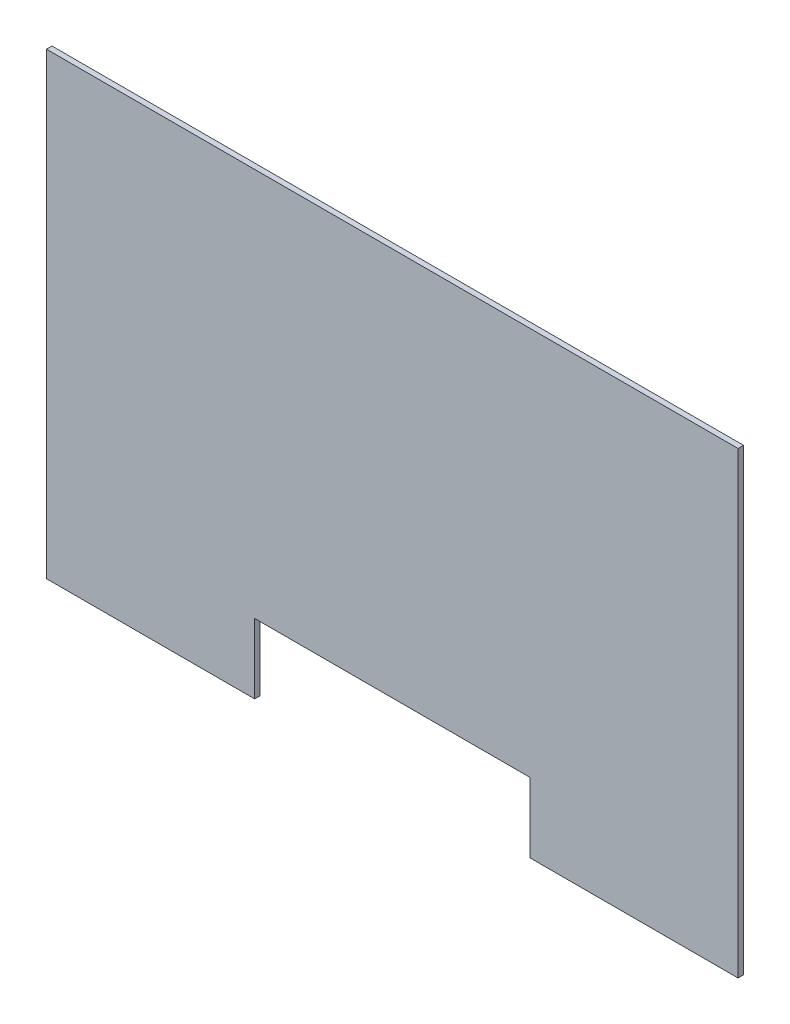
SolidWorks part; units mm, degrees
material "Alumina"
ref_plane "Front Plane" through (0, 0, 0) normal (0, 0, 1) x (1, 0, 0)
ref_plane "Top Plane" through (0, 0, 0) normal (0, 1, 0) x (1, 0, 0)
ref_plane "Right Plane" through (0, 0, 0) normal (1, 0, 0) x (0, 0, -1)
ref_axis "Axis X" through (57.4134, 0, 0) along (-1, 0, 0)
ref_axis "Axis Y" through (0, 65.1338, 0) along (0, -1, 0)
ref_axis "Axis Z" through (0, 0, -90.83) along (0, 0, 1)
sketch "Sketch1" plane through (0, 0, 0) normal (0, 0, 1) x (1, 0, 0)
  line L1 (-18.85, -12.5) -> (18.85, -12.5)
  line L2 (-18.85, -12.5) -> (-18.85, 12.5)
  line L3 (-18.85, 12.5) -> (18.85, 12.5)
  line L4 (18.85, -12.5) -> (18.85, 12.5)
  line L5 (-18.85, -12.5) -> (18.85, 12.5) construction
  line L6 (-18.85, 12.5) -> (18.85, -12.5) construction
  point P0 (0, 0)
  dimension "D1" = 37.7
  dimension "D2" = 25
extrude "Boss-Extrude1" add sketch "Sketch1" along normal blind 0.3
sketch "Sketch2" plane through (0, 0, 0.3) normal (0, 0, 1) x (1, 0, 0)
  line L0 (-18.85, -12.5) -> (18.85, -12.5) construction
  line L1 (-7.5, -8.7) -> (7.5, -8.7)
  line L2 (-7.5, -8.7) -> (-7.5, -14.7)
  line L3 (-7.5, -14.7) -> (7.5, -14.7)
  line L4 (7.5, -8.7) -> (7.5, -14.7)
  line L5 (0, -14.7) -> (0, 14.7) construction
  dimension "D1" = 15
  dimension "D2" = 3.8
  dimension "D3" = 6
extrude "Cut-Extrude1" cut sketch "Sketch2" against normal up to next
